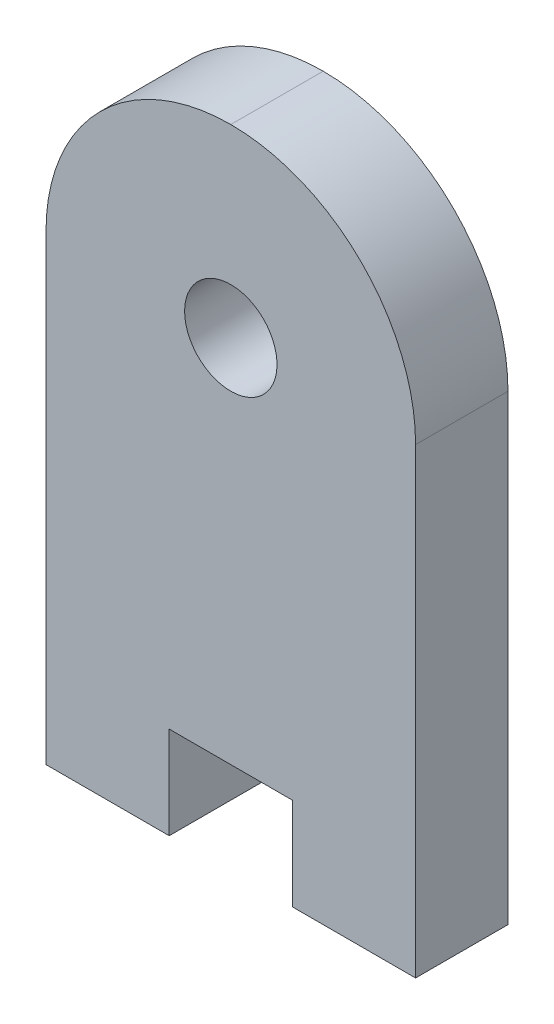
SolidWorks part; units mm, degrees
ref_plane "Front Plane" through (0, 0, 0) normal (0, 0, 1) x (1, 0, 0)
ref_plane "Top Plane" through (0, 0, 0) normal (0, 1, 0) x (1, 0, 0)
ref_plane "Right Plane" through (0, 0, 0) normal (1, 0, 0) x (0, 0, -1)
sketch "Sketch1" plane through (0, 0, 0) normal (0, 0, 1) x (1, 0, 0)
  line L1 (10, -15) -> (-10, -15)
  line L2 (10, -15) -> (10, 15)
  line L3 (10, 15) -> (-10, 15)
  line L4 (-10, -15) -> (-10, 15)
  line L5 (10, -15) -> (-10, 15) construction
  line L6 (10, 15) -> (-10, -15) construction
  point P0 (0, 0)
  dimension "D1" = 20
  dimension "D2" = 30
extrude "Boss-Extrude1" add sketch "Sketch1" along normal blind 5
fillet "Fillet2" radius 10 2 edges at (-10, 15, 2.5) (10, 15, 2.5)
sketch "Sketch2" plane through (0, 0, 0) normal (0, 0, -1) x (-1, 0, 0)
  circle A0 centre (0, 5) radius 2.5
  dimension "D1" = 5
extrude "Cut-Extrude1" cut sketch "Sketch2" against normal through all
sketch "Sketch3" plane through (0, -15, 0) normal (0, -1, 0) x (1, 0, 0)
  line L0 (-10, 0) -> (10, 0) construction
  line L1 (-10, 5) -> (-3.3333, 5)
  line L2 (-10, 5) -> (-10, 0)
  line L3 (-10, 0) -> (-3.3333, 0)
  line L4 (-3.3333, 5) -> (-3.3333, 0)
  line L6 (10, 5) -> (3.3333, 5)
  line L7 (10, 5) -> (10, 0)
  line L8 (10, 0) -> (3.3333, 0)
  line L9 (3.3333, 5) -> (3.3333, 0)
  dimension "D1" = 6.6667
  dimension "D2" = 6.6667
extrude "Boss-Extrude2" add sketch "Sketch3" along normal blind 5
